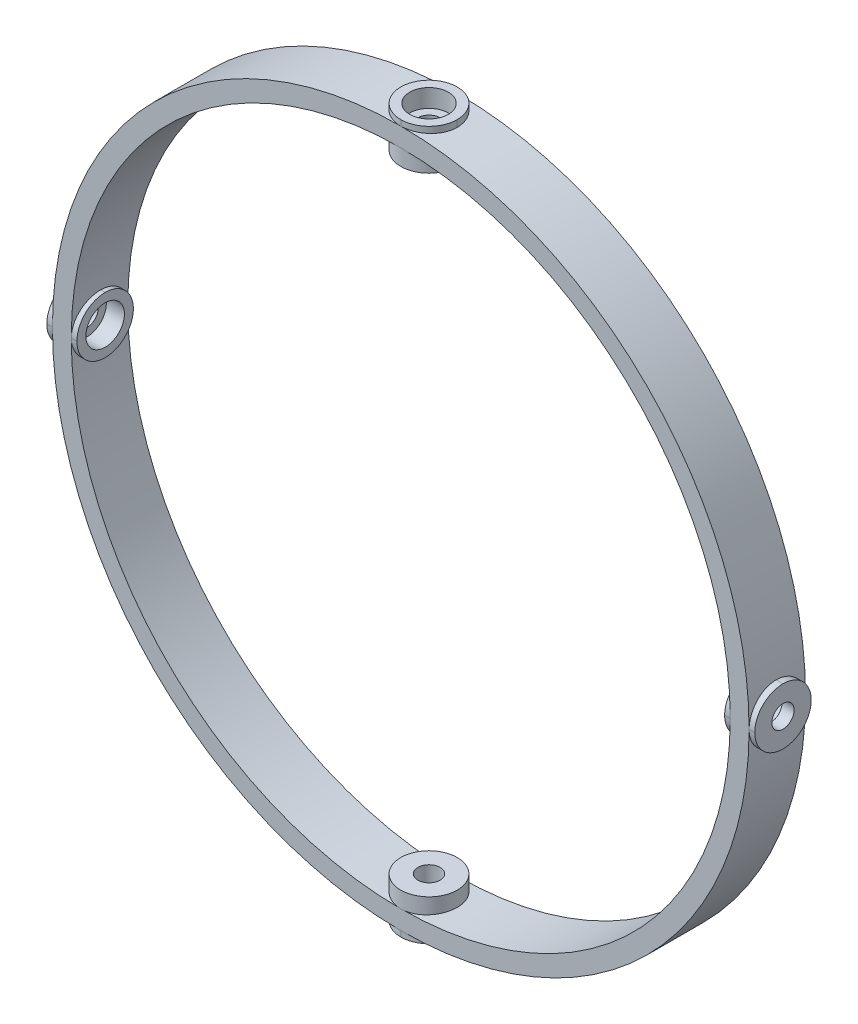
SolidWorks part; units mm, degrees
ref_plane "Front Plane" through (0, 0, 0) normal (0, 0, 1) x (1, 0, 0)
ref_plane "Top Plane" through (0, 0, 0) normal (0, 1, 0) x (1, 0, 0)
ref_plane "Right Plane" through (0, 0, 0) normal (1, 0, 0) x (0, 0, -1)
sketch "Sketch1" plane through (0, 0, 0) normal (0, 0, 1) x (1, 0, 0)
  circle A0 centre (0, 0) radius 58.7375
  circle A1 centre (0, 0) radius 55.5625
  dimension "D1" = 111.125
  dimension "D2" = 3.175
extrude "Boss-Extrude1" add sketch "Sketch1" along normal blind 9.525
sketch "Sketch2" plane through (0, 0, 9.525) normal (0, 0, 1) x (1, 0, 0)
  line L0 (0, 58.7375) -> (0, 55.5625) construction
  line L1 (0, -55.5625) -> (0, -58.7375) construction
  line L2 (58.7375, 0) -> (55.5625, 0) construction
  line L3 (-4.7625, -59.69) -> (4.7625, -59.69)
  line L4 (-4.7625, -59.69) -> (-4.7625, -54.61)
  line L5 (-4.7625, -54.61) -> (4.7625, -54.61)
  line L6 (4.7625, -59.69) -> (4.7625, -54.61)
  line L7 (-4.7625, -59.69) -> (4.7625, -54.61) construction
  line L8 (-4.7625, -54.61) -> (4.7625, -59.69) construction
  line L9 (-4.7625, 54.61) -> (4.7625, 54.61)
  line L10 (-4.7625, 54.61) -> (-4.7625, 59.69)
  line L11 (-4.7625, 59.69) -> (4.7625, 59.69)
  line L13 (-4.7625, 54.61) -> (4.7625, 59.69) construction
  line L14 (-4.7625, 59.69) -> (4.7625, 54.61) construction
  line L15 (-58.7375, 0) -> (-55.5625, 0) construction
  line L16 (59.69, 4.7625) -> (54.61, 4.7625)
  line L17 (-59.69, 4.7625) -> (-54.61, 4.7625)
  line L18 (-59.69, 4.7625) -> (-59.69, -4.7625)
  line L19 (-59.69, -4.7625) -> (-54.61, -4.7625)
  line L20 (-54.61, 4.7625) -> (-54.61, -4.7625)
  line L21 (-59.69, 4.7625) -> (-54.61, -4.7625) construction
  line L22 (-59.69, -4.7625) -> (-54.61, 4.7625) construction
  line L24 (54.61, 4.7625) -> (54.61, -4.7625)
  line L25 (54.61, -4.7625) -> (59.69, -4.7625)
  line L26 (59.69, 4.7625) -> (59.69, -4.7625)
  line L27 (54.61, 4.7625) -> (59.69, -4.7625) construction
  line L28 (54.61, -4.7625) -> (59.69, 4.7625) construction
  line L29 (4.7625, 59.69) -> (4.7625, 54.61)
  circle A0 centre (0, 0) radius 58.7375 construction
  circle A1 centre (0, 0) radius 55.5625 construction
  point P10 (0, -57.15)
  point P15 (0, 57.15)
  point P24 (-57.15, 0)
  point P29 (57.15, 0)
  dimension "D1" = 9.525
  dimension "D2" = 5.08
  dimension "D3" = 5.08
  dimension "0.375" = 9.525
extrude "Boss-Extrude2" add sketch "Sketch2" against normal up to surface (9.525 mm away) up to face at (58.7375, 0, 0)
sketch "Sketch3" plane through (0, -59.69, 0) normal (0, -1, 0) x (1, 0, 0)
  line L0 (0, 9.525) -> (0, 0) construction
  line L1 (-4.7625, 9.525) -> (4.7625, 9.525) construction
  line L2 (4.7625, 0) -> (-4.7625, 0) construction
  circle A0 centre (0, 4.7625) radius 1.875
  dimension "D1" = 3.75
extrude "Cut-Extrude1" cut sketch "Sketch3" against normal through all
sketch "Sketch6" plane through (-59.69, 0, 0) normal (-1, 0, 0) x (0, 0, 1)
  line L0 (0, 0) -> (9.525, 0) construction
  line L1 (0, -4.7625) -> (0, 4.7625) construction
  line L2 (9.525, 4.7625) -> (9.525, -4.7625) construction
  circle A0 centre (4.7625, 0) radius 1.875
  dimension "D1" = 3.75
extrude "Cut-Extrude4" cut sketch "Sketch6" against normal through all
sketch "Sketch4" plane through (0, -59.69, 0) normal (0, -1, 0) x (1, 0, 0)
  line L4 (-4.7625, 0) -> (4.7625, 0)
  line L5 (4.7625, 0) -> (4.7625, 9.525)
  line L6 (4.7625, 9.525) -> (-4.7625, 9.525)
  line L7 (-4.7625, 9.525) -> (-4.7625, 0)
  line L8 (-4.7625, 0) -> (4.7625, 0) construction
  line L9 (4.7625, 0) -> (4.7625, 9.525) construction
  line L10 (4.7625, 9.525) -> (-4.7625, 9.525) construction
  line L11 (-4.7625, 9.525) -> (-4.7625, 0) construction
  circle A0 centre (0, 4.7625) radius 1.875 construction
  circle A1 centre (0, 4.7625) radius 1.875 construction
  circle A2 centre (0, 4.7625) radius 3.25
  dimension "D2" = 6.5
  dimension "D1" = 0
extrude "Cut-Extrude2" cut sketch "Sketch4" against normal blind 3.048
sketch "Sketch5" plane through (0, 59.69, 0) normal (0, 1, 0) x (1, 0, 0)
  line L0 (0, -2.8875) -> (0, -6.6375) construction
  circle A0 centre (0, -4.7625) radius 1.875 construction
  circle A1 centre (0, -4.7625) radius 3.25
  circle A2 centre (0, -4.7625) radius 3.25 construction
extrude "Cut-Extrude3" cut sketch "Sketch5" against normal blind 3.048
sketch "Sketch10" plane through (54.61, 0, 0) normal (-1, 0, 0) x (0, 0, 1)
  circle A0 centre (4.7625, 0) radius 3.25
  dimension "D1" = 6.5
extrude "Cut-Extrude6" cut sketch "Sketch10" against normal blind 3.048
sketch "Sketch11" plane through (-54.61, 0, 0) normal (1, 0, 0) x (0, 0, -1)
  circle A0 centre (-4.7625, 0) radius 3.25
  circle A1 centre (-4.7625, 0) radius 3.25 construction
extrude "Cut-Extrude7" cut sketch "Sketch11" against normal blind 3.048
fillet "Fillet1" radius 4.7625 32 edges at (4.7625, -59.1171, 0) (-4.7625, -59.1171, 0) (-4.7625, -59.1171, 9.525) (4.7625, -59.1171, 9.525) (4.7625, -54.984, 9.525) (4.7625, -54.984, 0) (-4.7625, -54.984, 0) (-4.7625, -54.984, 9.525) (-4.7625, 59.1171, 9.525) (-4.7625, 59.1171, 0) (4.7625, 59.1171, 0) (4.7625, 59.1171, 9.525) (4.7625, 54.984, 0) (-4.7625, 54.984, 0) (4.7625, 54.984, 9.525) (-4.7625, 54.984, 9.525) (-54.984, -4.7625, 9.525) (-54.984, 4.7625, 9.525) (-54.984, -4.7625, 0) (-54.984, 4.7625, 0) (-59.1171, 4.7625, 9.525) (-59.1171, 4.7625, 0) (-59.1171, -4.7625, 9.525) (-59.1171, -4.7625, 0) (54.984, 4.7625, 0) (54.984, -4.7625, 0) (54.984, -4.7625, 9.525) (54.984, 4.7625, 9.525) (59.1171, 4.7625, 9.525) (59.1171, 4.7625, 0) (59.1171, -4.7625, 0) (59.1171, -4.7625, 9.525)
sketch "Sketch12" plane through (0, 54.61, 0) normal (0, -1, 0) x (1, 0, 0)
  circle A0 centre (0, 4.7625) radius 1.875 construction
  circle A1 centre (0, 4.7625) radius 1.875
  arc A4 (-4.7625, 4.7625) -> (0, 0) centre (0, 4.7625) ccw
  arc A5 (0, 0) -> (4.7625, 4.7625) centre (0, 4.7625) ccw
  arc A6 (4.7625, 4.7625) -> (0, 9.525) centre (0, 4.7625) ccw
  arc A7 (0, 9.525) -> (-4.7625, 4.7625) centre (0, 4.7625) ccw
  arc A8 (-4.7625, 4.7625) -> (0, 0) centre (0, 4.7625) ccw
  arc A9 (0, 0) -> (4.7625, 4.7625) centre (0, 4.7625) ccw
  arc A10 (4.7625, 4.7625) -> (0, 9.525) centre (0, 4.7625) ccw
  arc A11 (0, 9.525) -> (-4.7625, 4.7625) centre (0, 4.7625) ccw
  dimension "D1" = 0
extrude "Boss-Extrude3" add sketch "Sketch12" along normal blind 1.778
sketch "Sketch13" plane through (0, -54.61, 0) normal (0, 1, 0) x (1, 0, 0)
  circle A0 centre (0, -4.7625) radius 1.875 construction
  circle A1 centre (0, -4.7625) radius 1.875
  arc A4 (-4.7625, -4.7625) -> (0, -9.525) centre (0, -4.7625) ccw
  arc A5 (0, -9.525) -> (4.7625, -4.7625) centre (0, -4.7625) ccw
  arc A6 (4.7625, -4.7625) -> (0, 0) centre (0, -4.7625) ccw
  arc A7 (0, 0) -> (-4.7625, -4.7625) centre (0, -4.7625) ccw
  arc A8 (-4.7625, -4.7625) -> (0, -9.525) centre (0, -4.7625) ccw
  arc A9 (0, -9.525) -> (4.7625, -4.7625) centre (0, -4.7625) ccw
  arc A10 (4.7625, -4.7625) -> (0, 0) centre (0, -4.7625) ccw
  arc A11 (0, 0) -> (-4.7625, -4.7625) centre (0, -4.7625) ccw
  dimension "D1" = 0
extrude "Boss-Extrude4" add sketch "Sketch13" along normal blind 1.778
